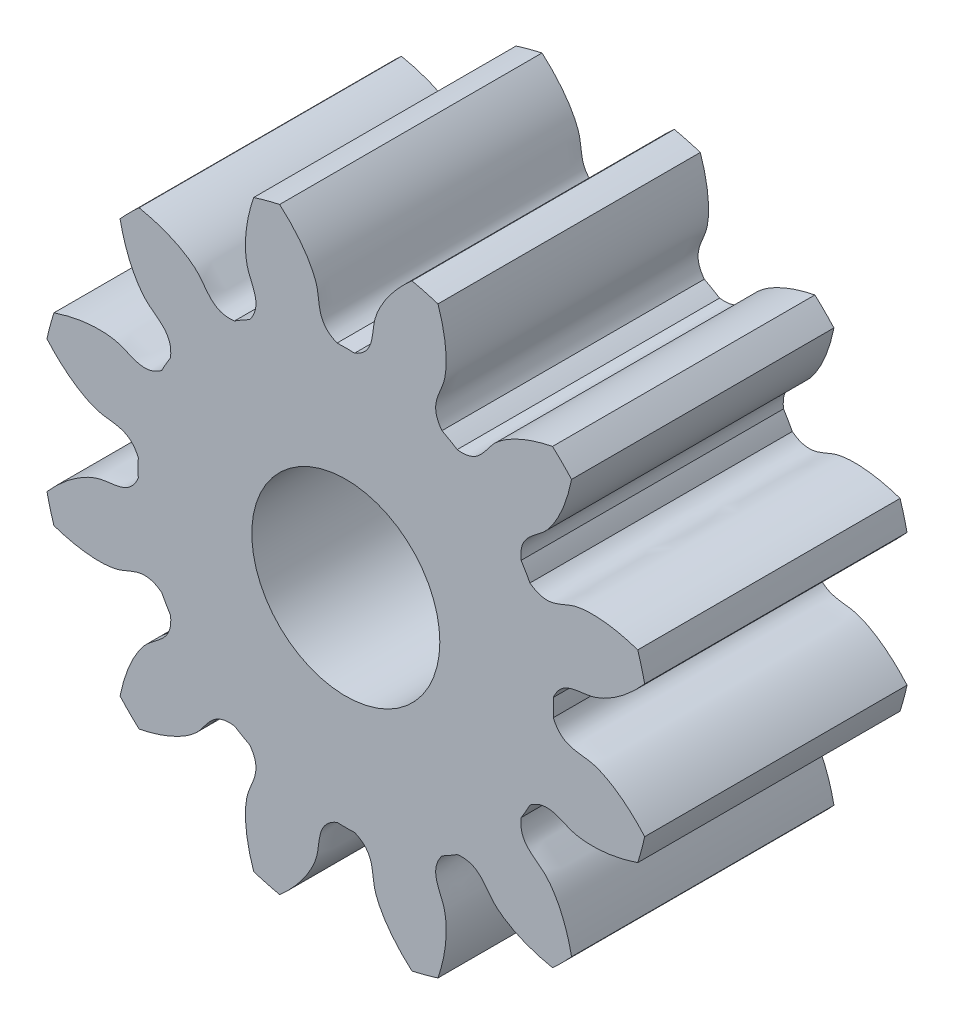
SolidWorks part; units mm, degrees
ref_plane "前视基准面" through (0, 0, 0) normal (0, 0, 1) x (1, 0, 0)
ref_plane "上视基准面" through (0, 0, 0) normal (0, 1, 0) x (1, 0, 0)
ref_plane "右视基准面" through (0, 0, 0) normal (1, 0, 0) x (0, 0, -1)
other "Configuration Table"
sketch "草图1" plane through (0, 0, 0) normal (0, 0, 1) x (1, 0, 0)
  circle A0 centre (0, 0) radius 3.5
extrude "凸台-拉伸1" add sketch "草图1" along normal blind 3
ref_axis "基准轴1" through (0, 0, 3) along (0, 0, -1)
sketch "草图2" plane through (0, 0, 0) normal (0, 0, 1) x (1, 0, 0)
  line L0 (0, 0) -> (0, 3.5) construction
  circle A0 centre (0, 0) radius 3.5 construction
  arc A1 (0.1004, 2.3729) -> (-0.1004, 2.3729) centre (0, 0) ccw
  arc A2 (1.7488, 3.9475) -> (-1.7488, 3.9475) centre (0, 0) ccw
  spline S0 degree 3 poles (0.1004, 2.3729) (0.3404, 2.4747) (0.2872, 2.6724) (0.3381, 2.8447) (0.3413, 2.855) (0.3451, 2.8662) (0.3495, 2.8784) (0.3546, 2.8915) (0.3603, 2.9056) (0.3668, 2.9206) (0.374, 2.9366) (0.3821, 2.9533) (0.3909, 2.971) (0.4007, 2.9894) (0.4114, 3.0086) (0.423, 3.0286) (0.4356, 3.0493) (0.4492, 3.0707) (0.4639, 3.0928) (0.4796, 3.1155) (0.4965, 3.1388) (0.5145, 3.1626) (0.5337, 3.187) (0.554, 3.2119) (0.5756, 3.2372) (0.5985, 3.2629) (0.6226, 3.289) (0.648, 3.3154) (0.6748, 3.342) (0.7028, 3.369) (0.7323, 3.3961) (0.7631, 3.4234) (0.7954, 3.4507) (0.829, 3.4782) (0.8641, 3.5057) (0.9006, 3.5331) (0.9385, 3.5604) (0.978, 3.5877) (1.0189, 3.6147) (1.0613, 3.6416) (1.1052, 3.6681) (1.1506, 3.6944) (1.1975, 3.7203) (1.2459, 3.7457) (1.2958, 3.7707) (1.3472, 3.7952) (1.4001, 3.8191) (1.4546, 3.8424) (1.5105, 3.865) (1.5679, 3.8869) (1.6472, 3.9154) (1.7078, 3.9351) (1.7488, 3.9475) knots 0 0 0 0 0.218015 0.222044 0.226546 0.231522 0.236972 0.242897 0.249295 0.256167 0.263513 0.271332 0.279626 0.288394 0.297636 0.307351 0.317541 0.328204 0.339341 0.350953 0.363038 0.375597 0.38863 0.402137 0.416118 0.430573 0.445502 0.460904 0.476781 0.493132 0.509956 0.527255 0.545027 0.563273 0.581994 0.601188 0.620856 0.640998 0.661614 0.682704 0.704268 0.726305 0.748817 0.771803 0.795262 0.819196 0.843603 0.868484 0.89384 0.919669 0.945972 1 1 1 1
  spline S1 degree 3 poles (-0.1004, 2.3729) (-0.3404, 2.4747) (-0.2872, 2.6724) (-0.3381, 2.8447) (-0.3413, 2.855) (-0.3451, 2.8662) (-0.3495, 2.8784) (-0.3546, 2.8915) (-0.3603, 2.9056) (-0.3668, 2.9206) (-0.374, 2.9366) (-0.3821, 2.9533) (-0.3909, 2.971) (-0.4007, 2.9894) (-0.4114, 3.0086) (-0.423, 3.0286) (-0.4356, 3.0493) (-0.4492, 3.0707) (-0.4639, 3.0928) (-0.4796, 3.1155) (-0.4965, 3.1388) (-0.5145, 3.1626) (-0.5337, 3.187) (-0.554, 3.2119) (-0.5756, 3.2372) (-0.5985, 3.2629) (-0.6226, 3.289) (-0.648, 3.3154) (-0.6748, 3.342) (-0.7028, 3.369) (-0.7323, 3.3961) (-0.7631, 3.4234) (-0.7954, 3.4507) (-0.829, 3.4782) (-0.8641, 3.5057) (-0.9006, 3.5331) (-0.9385, 3.5604) (-0.978, 3.5877) (-1.0189, 3.6147) (-1.0613, 3.6416) (-1.1052, 3.6681) (-1.1506, 3.6944) (-1.1975, 3.7203) (-1.2459, 3.7457) (-1.2958, 3.7707) (-1.3472, 3.7952) (-1.4001, 3.8191) (-1.4546, 3.8424) (-1.5105, 3.865) (-1.5679, 3.8869) (-1.6472, 3.9154) (-1.7078, 3.9351) (-1.7488, 3.9475) knots 0 0 0 0 0.218015 0.222044 0.226546 0.231522 0.236972 0.242897 0.249295 0.256167 0.263513 0.271332 0.279626 0.288394 0.297636 0.307351 0.317541 0.328204 0.339341 0.350953 0.363038 0.375597 0.38863 0.402137 0.416118 0.430573 0.445502 0.460904 0.476781 0.493132 0.509956 0.527255 0.545027 0.563273 0.581994 0.601188 0.620856 0.640998 0.661614 0.682704 0.704268 0.726305 0.748817 0.771803 0.795262 0.819196 0.843603 0.868484 0.89384 0.919669 0.945972 1 1 1 1
extrude "切除-拉伸1" cut sketch "草图2" along normal through all
pattern_circular "阵列(圆周)1" count 12 every 30 about axis through (0, 0, 3) along (0, 0, -1) of "切除-拉伸1"
sketch "草图3" plane through (0, 0, 0) normal (0, 0, 1) x (1, 0, 0)
  circle A0 centre (0, 0) radius 3 construction
  dimension "Dn" = 6
sketch "草图5" plane through (0, 0, 3) normal (0, 0, 1) x (1, 0, 0)
  circle A0 centre (0, 0) radius 1.075
  dimension "D1" = 2.15
extrude "切除-拉伸2" cut sketch "草图5" against normal up to next
